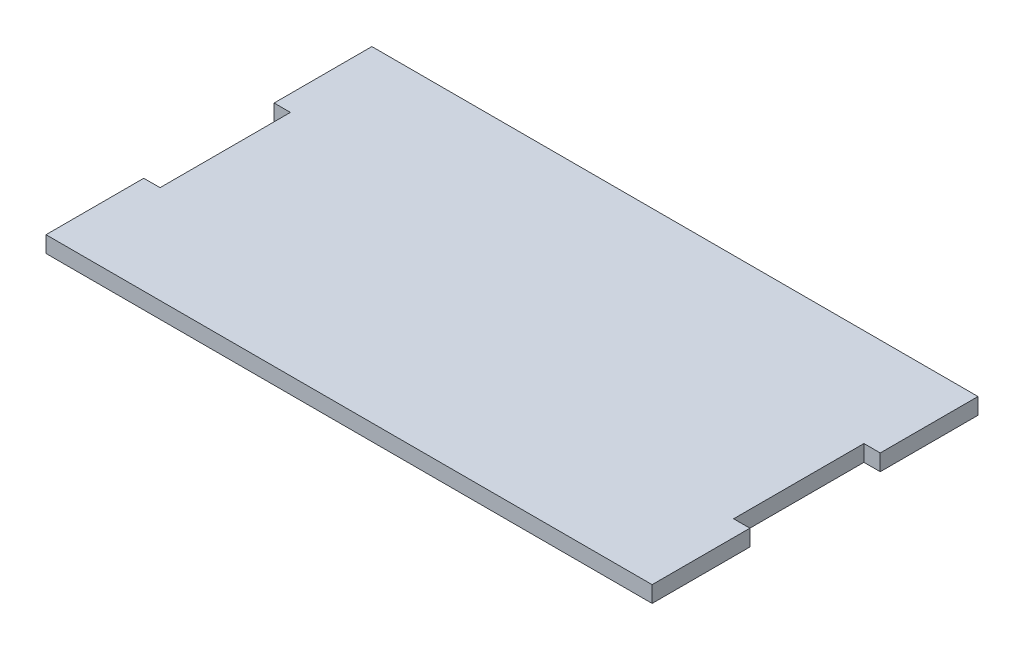
SolidWorks part; units mm, degrees
ref_plane "Front" through (0, 0, 0) normal (0, 0, 1) x (1, 0, 0)
ref_plane "Top" through (0, 0, 0) normal (0, 1, 0) x (1, 0, 0)
ref_plane "Right" through (0, 0, 0) normal (1, 0, 0) x (0, 0, -1)
sketch "Skizze1" plane through (0, 0, 0) normal (0, 1, 0) x (1, 0, 0)
  line L1 (0, 0) -> (186, 0)
  line L2 (0, 0) -> (0, 100)
  line L3 (0, 100) -> (186, 100)
  line L4 (186, 0) -> (186, 100)
  dimension "D1" = 100
  dimension "D2" = 186
extrude "Aufsatz-Linear austragen1" add sketch "Skizze1" along normal blind 5
sketch "Skizze2" plane through (0, 5, 0) normal (0, 1, 0) x (1, 0, 0)
  line L0 (186, 50) -> (93, 50) construction
  line L1 (186, 0) -> (186, 100) construction
  line L2 (93, 50) -> (93, 0) construction
  line L3 (0, 0) -> (186, 0) construction
  line L4 (186, 70) -> (186, 30)
  line L5 (186, 30) -> (181, 30)
  line L6 (181, 30) -> (181, 70)
  line L7 (186, 70) -> (181, 70)
  line L8 (0, 70) -> (5, 70)
  line L9 (5, 30) -> (5, 70)
  line L10 (0, 30) -> (5, 30)
  line L11 (0, 70) -> (0, 30)
  point P11 (181, 50)
  point P16 (5, 50)
  dimension "D1" = 5
  dimension "D2" = 40
extrude "Schnitt-Linear austragen1" cut sketch "Skizze2" against normal through all
sketch "Skizze3" [suppressed] plane through (0, 5, 0) normal (0, 1, 0) x (1, 0, 0)
  line L0 (0, 0) -> (120, 0) construction
  line L1 (90, 0) -> (0, 0)
  line L2 (90, 0) -> (90, 65)
  line L3 (90, 65) -> (0, 65)
  line L4 (0, 0) -> (0, 65)
  line L5 (120, 0) -> (120, 12.5) construction
  dimension "D1" = 30
extrude "Schnitt-Linear austragen2" [suppressed] cut sketch "Skizze3" against normal through all
